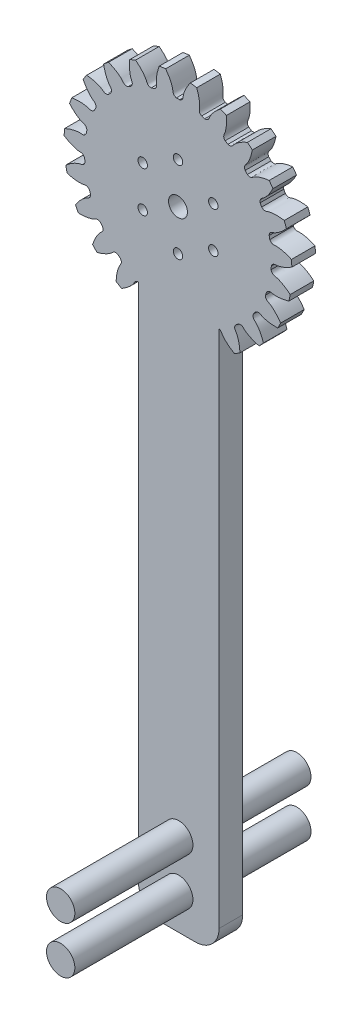
SolidWorks part; units mm, degrees
ref_plane "前视基准面" through (0, 0, 0) normal (0, 0, 1) x (1, 0, 0)
ref_plane "上视基准面" through (0, 0, 0) normal (0, 1, 0) x (1, 0, 0)
ref_plane "右视基准面" through (0, 0, 0) normal (1, 0, 0) x (0, 0, -1)
sketch "草图1" plane through (0, 0, 0) normal (0, 0, 1) x (1, 0, 0)
  circle A0 centre (0, 0) radius 48.25
extrude "凸台-拉伸1" add sketch "草图1" along normal blind 10
ref_axis "基准轴1" through (0, 0, -1.5) along (0, 0, 1)
sketch "草图2" plane through (0, 0, 0) normal (0, 0, 1) x (1, 0, 0)
  line L0 (0, 0) -> (0, 48.25) construction
  circle A0 centre (0, 0) radius 48.25 construction
  arc A1 (0.7001, 39.5588) -> (-0.7001, 39.5588) centre (0, 0) ccw
  arc A2 (12.2813, 54.7587) -> (-12.2813, 54.7587) centre (0, 0) ccw
  spline S0 degree 3 poles (0.7001, 39.5588) (2.2301, 40.0157) (2.0989, 41.0466) (2.2887, 42.0631) (2.3141, 42.1856) (2.3456, 42.3239) (2.3839, 42.4778) (2.4296, 42.6469) (2.4833, 42.8311) (2.5457, 43.0301) (2.6174, 43.2437) (2.6989, 43.4715) (2.791, 43.7132) (2.894, 43.9685) (3.0088, 44.237) (3.1357, 44.5184) (3.2754, 44.8123) (3.4283, 45.1182) (3.5952, 45.4358) (3.7764, 45.7646) (3.9725, 46.1042) (4.1839, 46.4541) (4.4112, 46.8137) (4.6549, 47.1827) (4.9154, 47.5605) (5.1931, 47.9465) (5.4885, 48.3403) (5.802, 48.7412) (6.1339, 49.1487) (6.4848, 49.5622) (6.8549, 49.9811) (7.2445, 50.4049) (7.6542, 50.8328) (8.084, 51.2642) (8.5345, 51.6985) (9.0057, 52.1351) (9.4981, 52.5733) (10.0118, 53.0124) (10.5471, 53.4517) (11.2986, 54.0437) (11.8822, 54.4754) (12.2813, 54.7587) knots 0 0 0 0 0.147387 0.15296 0.159389 0.166677 0.174821 0.183823 0.193683 0.204399 0.215973 0.228404 0.241693 0.255839 0.270842 0.286703 0.303421 0.320996 0.339428 0.358718 0.378866 0.39987 0.421732 0.444451 0.468028 0.492462 0.517753 0.543901 0.570907 0.59877 0.627491 0.657069 0.687504 0.718796 0.750946 0.783953 0.817818 0.85254 0.888119 0.924555 1 1 1 1
  spline S1 degree 3 poles (-0.7001, 39.5588) (-2.2301, 40.0157) (-2.0989, 41.0466) (-2.2887, 42.0631) (-2.3141, 42.1856) (-2.3456, 42.3239) (-2.3839, 42.4778) (-2.4296, 42.6469) (-2.4833, 42.8311) (-2.5457, 43.0301) (-2.6174, 43.2437) (-2.6989, 43.4715) (-2.791, 43.7132) (-2.894, 43.9685) (-3.0088, 44.237) (-3.1357, 44.5184) (-3.2754, 44.8123) (-3.4283, 45.1182) (-3.5952, 45.4358) (-3.7764, 45.7646) (-3.9725, 46.1042) (-4.1839, 46.4541) (-4.4112, 46.8137) (-4.6549, 47.1827) (-4.9154, 47.5605) (-5.1931, 47.9465) (-5.4885, 48.3403) (-5.802, 48.7412) (-6.1339, 49.1487) (-6.4848, 49.5622) (-6.8549, 49.9811) (-7.2445, 50.4049) (-7.6542, 50.8328) (-8.084, 51.2642) (-8.5345, 51.6985) (-9.0057, 52.1351) (-9.4981, 52.5733) (-10.0118, 53.0124) (-10.5471, 53.4517) (-11.2986, 54.0437) (-11.8822, 54.4754) (-12.2813, 54.7587) knots 0 0 0 0 0.147387 0.15296 0.159389 0.166677 0.174821 0.183823 0.193683 0.204399 0.215973 0.228404 0.241693 0.255839 0.270842 0.286703 0.303421 0.320996 0.339428 0.358718 0.378866 0.39987 0.421732 0.444451 0.468028 0.492462 0.517753 0.543901 0.570907 0.59877 0.627491 0.657069 0.687504 0.718796 0.750946 0.783953 0.817818 0.85254 0.888119 0.924555 1 1 1 1
extrude "切除-拉伸1" cut sketch "草图2" along normal through all
pattern_circular "阵列(圆周)1" count 23 every 15.652 about axis through (0, 0, -1.5) along (0, 0, 1) of "切除-拉伸1"
sketch "草图3" plane through (0, 0, 0) normal (0, 0, 1) x (1, 0, 0)
  circle A0 centre (0, 0) radius 44.39 construction
  dimension "Dn" = 88.78
sketch "草图4" plane through (0, 0, 10) normal (0, 0, 1) x (1, 0, 0)
  line L0 (-34.3139, -33.9207) -> (34.3139, -33.9207)
  line L1 (-34.3139, -33.9207) -> (-34.3139, -273.9207)
  line L2 (34.3139, -33.9207) -> (34.3139, -273.9207)
  line L3 (-34.3139, -273.9207) -> (34.3139, -273.9207)
sketch "草图5" plane through (0, 0, 10) normal (0, 0, 1) x (1, 0, 0)
  line L0 (0, 0) -> (48.2116, 0) construction
  line L1 (0, 0) -> (-43.3557, 0) construction
  line L3 (-16.7626, 0) -> (17.3985, 0)
  line L4 (-16.7626, 0) -> (-16.7626, -266)
  line L5 (-16.7626, -266) -> (17.3985, -266)
  line L6 (17.3985, 0) -> (17.3985, -266)
  dimension "D1" = 266
extrude "凸台-拉伸5" add sketch "草图5" against normal blind 10
sketch "草图6" plane through (0, 0, 10) normal (0, 0, 1) x (1, 0, 0)
  circle A0 centre (0, 0) radius 17.25 construction
  circle A1 centre (0, 17.25) radius 2
  circle A2 centre (14.9389, 8.625) radius 2
  circle A3 centre (14.9389, -8.625) radius 2
  circle A4 centre (0, -17.25) radius 2
  circle A5 centre (-14.9389, -8.625) radius 2
  circle A6 centre (-14.9389, 8.625) radius 2
  point P17 (0, 0)
  dimension "D1" = 34.5
  dimension "D2" = 6
extrude "切除-拉伸3" cut sketch "草图6" against normal blind 169
sketch "草图7" plane through (0, 0, 0) normal (0, 0, -1) x (-1, 0, 0)
  circle A0 centre (0, 0) radius 29.5
  dimension "D1" = 59
sketch "草图14" plane through (0, 0, 10) normal (0, 0, 1) x (1, 0, 0)
  line L0 (0.3179, -266) -> (0.3179, -251) construction
  line L1 (-16.7626, -266) -> (17.3985, -266) construction
  line L2 (0.3179, -251) -> (0.3179, -231) construction
  circle A0 centre (0.3179, -251) radius 6
  circle A1 centre (0.3179, -231) radius 6
  dimension "D2" = 20
  dimension "D1" = 15
extrude "凸台-拉伸8" add sketch "草图14" along normal mid plane 100
sketch "草图15" plane through (0, 0, 0) normal (0, 0, -1) x (-1, 0, 0)
  circle A0 centre (0, 0) radius 4
extrude "切除-拉伸4" cut sketch "草图15" against normal blind 27
sketch "草图17" plane through (0, 0, 10) normal (0, 0, 1) x (1, 0, 0)
  circle A0 centre (0, 0) radius 4
fillet "圆角1" radius 10 1 edges at (-16.7626, -266, 5) type face fillet first side face at (-16.7626, -150.9903, 5) second side face at (0.3179, -266, 5)
fillet "圆角2" radius 10 1 edges at (17.3985, -266, 5) type face fillet first side face at (5.3179, -266, 5) second side face at (17.3985, -151.0329, 5)
